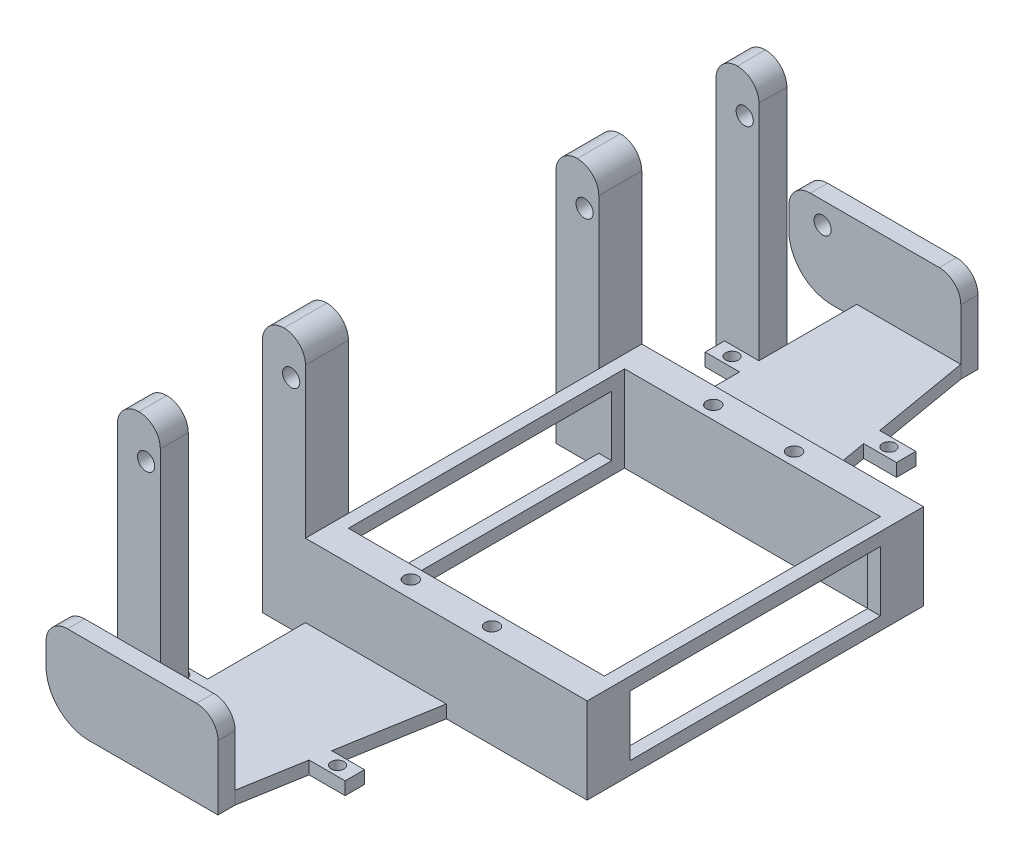
SolidWorks part; units mm, degrees
ref_plane "Front Plane" through (0, 0, 0) normal (0, 0, 1) x (1, 0, 0)
ref_plane "Top Plane" through (0, 0, 0) normal (0, 1, 0) x (1, 0, 0)
ref_plane "Right Plane" through (0, 0, 0) normal (1, 0, 0) x (0, 0, -1)
sketch "Sketch1" plane through (0, 0, 0) normal (0, 1, 0) x (1, 0, 0)
  line L0 (0, 39.1145) -> (0, -39.1145)
  line L1 (0, -39.1145) -> (65.532, -39.1145)
  line L2 (65.532, -39.1145) -> (65.532, 39.1145)
  line L3 (65.532, 39.1145) -> (0, 39.1145)
  line L4 (0, 39.1145) -> (0, 89.1145)
  line L5 (0, 89.1145) -> (24.2, 89.1145)
  line L6 (24.2, 89.1145) -> (32.766, 39.1145)
  line L7 (0, 39.1145) -> (32.766, 39.1145)
  line L8 (0, -39.1145) -> (0, -89.1145)
  line L9 (-8, 66.3645) -> (8, 66.3645)
  line L10 (-8, 66.3645) -> (-8, 61.8645)
  line L11 (-8, 61.8645) -> (8, 61.8645)
  line L12 (8, 66.3645) -> (8, 61.8645)
  line L13 (-55, 0) -> (55, 0) construction
  line L14 (3, 32.1145) -> (62.532, 32.1145)
  line L15 (20.483, 66.3645) -> (36.483, 66.3645)
  line L16 (20.483, 66.3645) -> (20.483, 61.8645)
  line L17 (20.483, 61.8645) -> (36.483, 61.8645)
  line L18 (36.483, 66.3645) -> (36.483, 61.8645)
  line L19 (3, 32.1145) -> (3, -32.1145)
  line L20 (3, -32.1145) -> (62.532, -32.1145)
  line L21 (0, -55) -> (0, 55) construction
  line L22 (0, -89.1145) -> (24.2, -89.1145)
  line L23 (24.2, -89.1145) -> (32.766, -39.1145)
  line L24 (32.766, -39.1145) -> (0, -39.1145)
  line L25 (62.532, 32.1145) -> (62.532, -32.1145)
  line L26 (20.483, -61.8645) -> (36.483, -61.8645)
  line L27 (20.483, -61.8645) -> (20.483, -66.3645)
  line L28 (20.483, -66.3645) -> (36.483, -66.3645)
  line L29 (36.483, -61.8645) -> (36.483, -66.3645)
  line L30 (3, 32.1145) -> (62.532, -32.1145) construction
  line L31 (3, -32.1145) -> (62.532, 32.1145) construction
  line L32 (-8, -61.8645) -> (8, -61.8645)
  line L33 (-8, -61.8645) -> (-8, -66.3645)
  line L34 (-8, -66.3645) -> (8, -66.3645)
  line L35 (8, -61.8645) -> (8, -66.3645)
  line L36 (0, 89.1145) -> (0, 91.1145)
  line L37 (0, 91.1145) -> (24.2, 91.1145)
  line L38 (24.2, 91.1145) -> (24.2, 89.1145)
  line L39 (0, -89.1145) -> (0, -81.0311)
  line L40 (0, -81.0311) -> (37.5753, -81.0311)
  line L41 (37.5753, -81.0311) -> (37.5753, -89.1145)
  line L42 (37.5753, -89.1145) -> (0, -89.1145)
  line L43 (32.766, 39.1145) -> (0, 39.1145)
  line L44 (32.766, -39.1145) -> (0, -39.1145)
  circle A0 centre (20.574, 35.1758) radius 1.6
  circle A1 centre (39.37, 35.1758) radius 1.5999
  circle A2 centre (20.574, -35.1795) radius 1.6
  circle A3 centre (39.4509, -35.1795) radius 1.5999
  circle A4 centre (-4, 64.1145) radius 1.5
  circle A5 centre (32.483, 64.1145) radius 1.5
  circle A6 centre (-4, -64.1145) radius 1.5
  circle A8 centre (32.483, -64.1145) radius 1.5
  point P8 (0, 64.1145)
  point P21 (28.483, 64.1145)
  point P30 (28.483, -64.1145)
  point P40 (0, -64.1145)
  point P47 (32.766, 0)
  dimension "D12" = 3
  dimension "D14" = 3
  dimension "D23" = 3
  dimension "D24" = 4
  dimension "D26" = 3
  dimension "D27" = 7
  dimension "D1" = 65.532
  dimension "D2" = 78.229
  dimension "D3" = 50
  dimension "D4" = 24.2
  dimension "D5" = 7
  dimension "D6" = 50
  dimension "D7" = 16
  dimension "D8" = 16
  dimension "D9" = 4.5
  dimension "D10" = 4.5
  dimension "D11" = 8
  dimension "D13" = 4
  dimension "D15" = 4
  dimension "D16" = 44.483
  dimension "D17" = 50
  dimension "D18" = 70.3553
  dimension "D19" = 16
  dimension "D20" = 16
  dimension "D21" = 4.5
  dimension "D22" = 4.5
  dimension "D25" = 4
  dimension "D28" = 3
  dimension "D29" = 3
  dimension "D30" = 2.25
  dimension "D31" = 2.25
  dimension "D32" = 2.25
  dimension "D33" = 2.25
  dimension "D34" = 36.483
  dimension "D35" = 36.483
  dimension "D36" = 2
  dimension "D37" = 3.935
extrude "Boss-Extrude1" add sketch "Sketch1" along normal blind 3 contours L10 L11 L4 L9 A4 | L12 L9 L4 L11 | L17 L16 L15 L6 L5 L4 L9 L12 L11 L3 | L16 L17 L6 L15 | L18 L15 L6 L17 A5 | L2 L3 L0 L1 A3 A2 A1 A0 L14 L25 L20 L19 | L32 L35 L34 L8 L22 L23 L28 L27 L26 L1 | L27 L28 L23 L26 | L29 L26 L23 L28 A8 | L35 L32 L8 L34 | L33 L34 L8 L32 A6 region at (16.383, 0, -38.094) region at (14.3545, 0, -62.7957) region at (14.6875, 0, 58.9075) region at (-4, 0, -61.9563) region at (4, 0, -64.1145) region at (4, 0, 64.1145) region at (-0.0918, 0, 64.1145) region at (24.4861, 0, -64.0784) region at (28.5768, 0, -64.1306) region at (32.6757, 0, 61.9597) region at (24.4861, 0, 64.0784)
sketch "Sketch2" plane through (0, 0, 0) normal (0, 1, 0) x (1, 0, 0)
  line L11 (25.5849, -81.0373) -> (25.5849, -85.0373)
  line L12 (25.5849, -85.0373) -> (-14.4151, -85.0373)
  line L13 (-14.4151, -85.0373) -> (-14.4151, -81.0373)
  line L14 (-14.4151, -81.0373) -> (25.5849, -81.0373)
  line L15 (24.2, 89.1145) -> (24.2, 93.1145)
  line L16 (24.2, 93.1145) -> (-15.8, 93.1145)
  line L17 (-15.8, 93.1145) -> (-15.8, 89.1145)
  line L18 (-15.8, 89.1145) -> (24.2, 89.1145)
  dimension "D1" = 40
  dimension "D2" = 4
  dimension "D3" = 40
  dimension "D4" = 4
extrude "Boss-Extrude2" add sketch "Sketch2" along normal blind 20
sketch "Sketch3" plane through (0, 0, 0) normal (0, 0, 1) x (1, 0, 0)
  line L2 (0, -16.5) -> (0, 16.5) construction
  circle A4 centre (0, 14.8653) radius 2
  dimension "D4" = 4
fillet "Fillet2" radius 5 2 edges at (25.5849, 20, 83.0373) (-14.4151, 20, 83.0373)
fillet "Fillet3" radius 10 1 edges at (-14.4151, 0, 83.0373)
extrude "Boss-Extrude3" add sketch "Sketch1<8>" along normal blind 20 contours L2 L3 L0 L1 A3 A2 A1 A0 L14 L25 L20 L19 region at (16.383, 0, -38.094)
sketch "Sketch1<8>" plane through (0, 0, 0) normal (0, 1, 0) x (1, 0, 0) same geometry as "Sketch1"
sketch "Sketch5" plane through (0, 0, 0) normal (0, 1, 0) x (1, 0, 0)
  circle A0 centre (20.574, -35.1795) radius 2.5
  circle A1 centre (39.4509, -35.1795) radius 2.5
  circle A2 centre (20.574, 35.1758) radius 2.5
  circle A3 centre (39.37, 35.1758) radius 2.5
  dimension "D1" = 5
extrude "Cut-Extrude2" cut sketch "Sketch5" along normal blind 5
sketch "Sketch7" plane through (0, 0, 0) normal (1, 0, 0) x (0, 0, -1)
  line L0 (-29.1145, 17) -> (-29.1145, 3)
  line L1 (-29.1145, 3) -> (29.1145, 3)
  line L2 (29.1145, 3) -> (29.1145, 17)
  line L3 (29.1145, 17) -> (-29.1145, 17)
  line L4 (-39.1145, 20) -> (-39.1145, 0) construction
  line L5 (39.1145, 20) -> (39.1145, 0) construction
  line L6 (-39.1145, 20) -> (39.1145, 20) construction
  line L7 (55, 0) -> (-55, 0) construction
  dimension "D1" = 10
  dimension "D2" = 10
  dimension "D3" = 3
  dimension "D4" = 3
extrude "Cut-Extrude3" cut sketch "Sketch7" along normal through all
sketch "Sketch8" plane through (0, 0, -93.1145) normal (0, 0, -1) x (-1, 0, 0)
  line L1 (15.8, 0) -> (-24.2, 0) construction
  circle A0 centre (7.9316, 15) radius 2
  point P2 (7.3597, 14.8653)
  point P3 (7.8891, 15)
  point P6 (0, 0)
  point P7 (0, 0)
  point P8 (7.9316, 15)
  dimension "D1" = 4
  dimension "D2" = 15
extrude "Cut-Extrude4" cut sketch "Sketch8" against normal blind 211
fillet "Fillet4" radius 10 1 edges at (-15.8, 0, -91.1145)
fillet "Fillet5" radius 5 2 edges at (24.2, 20, -91.1145) (-15.8, 20, -91.1145)
sketch "Sketch9" plane through (0, 0, 0) normal (-1, 0, 0) x (0, 0, 1)
  line L1 (-39.1145, 0) -> (-29.1145, 0)
  line L2 (-39.1145, 0) -> (-39.1145, 59.863)
  line L3 (-39.1145, 59.863) -> (-29.1145, 59.863)
  line L4 (-29.1145, 0) -> (-29.1145, 59.863)
  line L5 (61.8645, 0) -> (-61.8645, 0) construction
  line L6 (-29.1145, 3) -> (-29.1145, 17) construction
  point P5 (-29.0945, 0)
  point P7 (-29.0635, 0)
extrude "Boss-Extrude4" add sketch "Sketch9" along normal blind 10
sketch "Sketch12" plane through (0, 0, 0) normal (-1, 0, 0) x (0, 0, 1)
  line L0 (-29.1145, 59.863) -> (-39.1145, 59.863) construction
  line L1 (-66.3645, 0) -> (-72.8645, 0)
  line L2 (-66.3645, 0) -> (-66.3645, 59.863)
  line L3 (-66.3645, 59.863) -> (-72.8645, 59.863)
  line L4 (-72.8645, 0) -> (-72.8645, 59.863)
  dimension "D1" = 6.5
  dimension "D2" = 0
extrude "Boss-Extrude6" add sketch "Sketch12" along normal blind 10
sketch "Sketch10" plane through (0, 0, -39.1145) normal (0, 0, -1) x (-1, 0, 0)
  circle A0 centre (3.3116, 50.6914) radius 2
extrude "Cut-Extrude5" cut sketch "Sketch10" against normal through all both and the other way through all
fillet "Fillet9" radius 5 4 edges at (0, 59.863, -69.6145) (0, 59.863, -34.1145) (-10, 59.863, -69.6145) (-10, 59.863, -34.1145)
mirror "Mirror1" about plane through (0, 0, 0) normal (0, 0, 1) of "Cut-Extrude5", "Fillet9", "Boss-Extrude6", "Boss-Extrude4"
